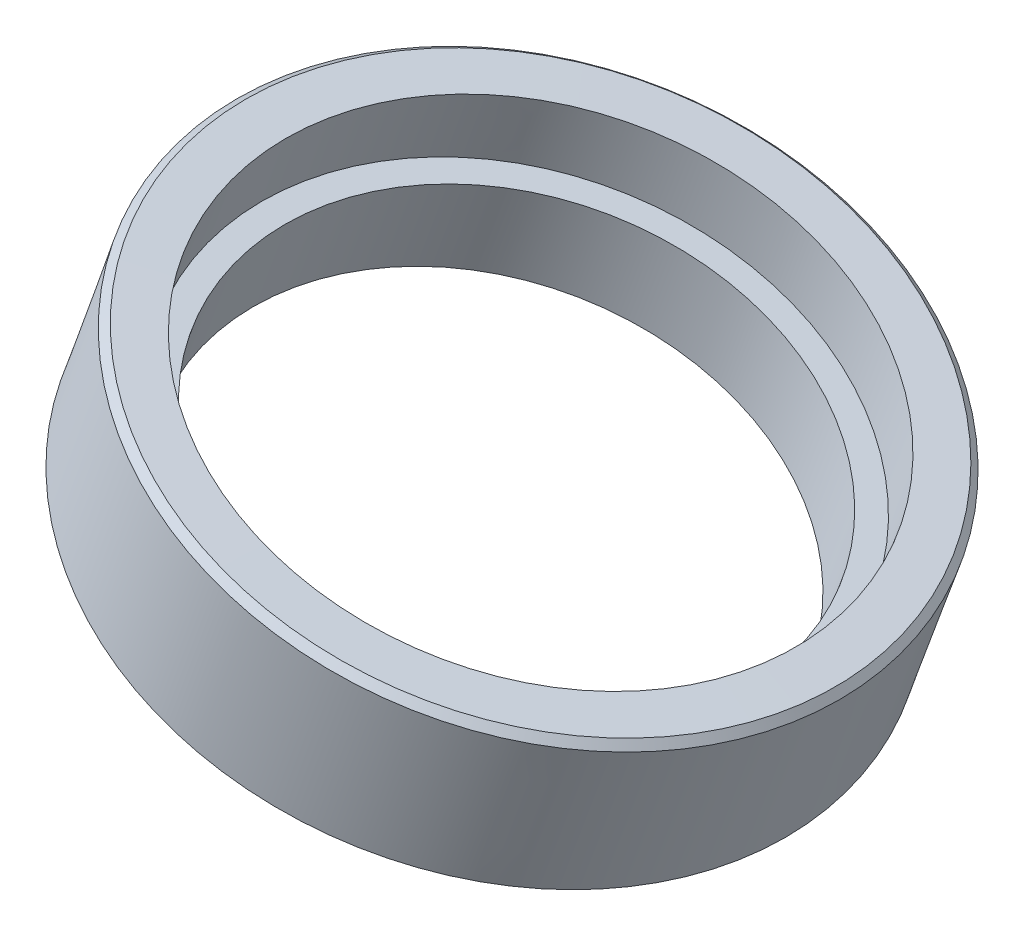
SolidWorks part; units mm, degrees
ref_plane "Přední rovina" through (0, 0, 0) normal (0, 0, 1) x (1, 0, 0)
ref_plane "Horní rovina" through (0, 0, 0) normal (0, 1, 0) x (1, 0, 0)
ref_plane "Pravá rovina" through (0, 0, 0) normal (1, 0, 0) x (0, 0, -1)
sketch "Skica2" plane through (0, 0, 0) normal (0, 0, 1) x (1, 0, 0)
  line L0 (-356.7602, -28.0701) -> (-358.4905, -32.7612)
  line L2 (-358.4905, -32.7612) -> (-360.1333, -32.1632)
  line L3 (-360.1333, -32.1632) -> (-362.5566, -38.821)
  line L4 (-362.5566, -38.821) -> (-357.6535, -40.6056)
  line L5 (-357.6535, -40.6056) -> (-353.4765, -29.2813)
  line L6 (-353.4765, -29.2813) -> (-356.7602, -28.0701)
  line L7 (-354.4147, -28.9353) -> (-351.9922, -22.3678) construction
  line L9 (-372.8806, -16.0194) -> (-374.7984, -21.2885) construction
  line L10 (-372.8806, -16.0194) -> (-385.9489, -51.9243) construction
  line L11 (-365.4206, -45.2279) -> (-397.3701, -33.5992) construction
  dimension "D1" = 1
  dimension "D2" = 7
  dimension "D3" = 35
revolve "Rotovat1" add sketch "Skica2" angle 360 about L10
cosmetic thread "Kosmetický závit1" parameters "D2"=35.513
chamfer "Zkosení1" distance 0.5 angle 45 2 edges at (-396.2696, -13.7059, 0) (-400.3489, -25.0658, 0) first distance on face at (-392.9756, -14.8888, 0) first distance on face at (-400.3489, -25.0658, 0)
chamfer "Zkosení2" distance 0.5 angle 45 1 edges at (-395.4458, -26.8503, 0)
